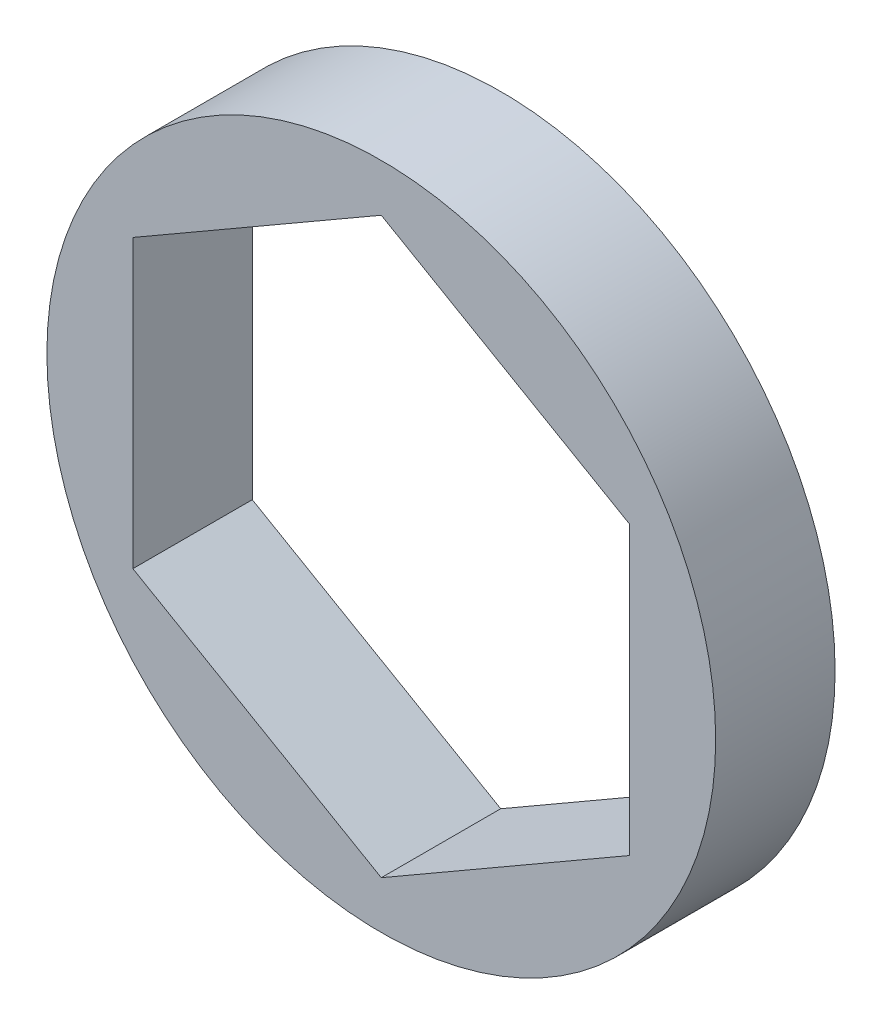
SolidWorks part; units mm, degrees
material "PET"
ref_plane "Front Plane" through (0, 0, 0) normal (0, 0, 1) x (1, 0, 0)
ref_plane "Top Plane" through (0, 0, 0) normal (0, 1, 0) x (1, 0, 0)
ref_plane "Right Plane" through (0, 0, 0) normal (1, 0, 0) x (0, 0, -1)
sketch "Sketch1" plane through (0, 0, 0) normal (0, 0, 1) x (1, 0, 0)
  line L1 (0, 7.6256) -> (-6.604, 3.8128)
  line L2 (-6.604, 3.8128) -> (-6.604, -3.8128)
  line L3 (-6.604, -3.8128) -> (0, -7.6256)
  line L4 (0, -7.6256) -> (6.604, -3.8128)
  line L5 (6.604, -3.8128) -> (6.604, 3.8128)
  line L6 (6.604, 3.8128) -> (0, 7.6256)
  circle A0 centre (0, 0) radius 6.604 construction
  circle A1 centre (0, 0) radius 8.89
  dimension "D1" = 13.208
  dimension "D2" = 17.78
extrude "Boss-Extrude1" add sketch "Sketch1" along normal mid plane 3.175
